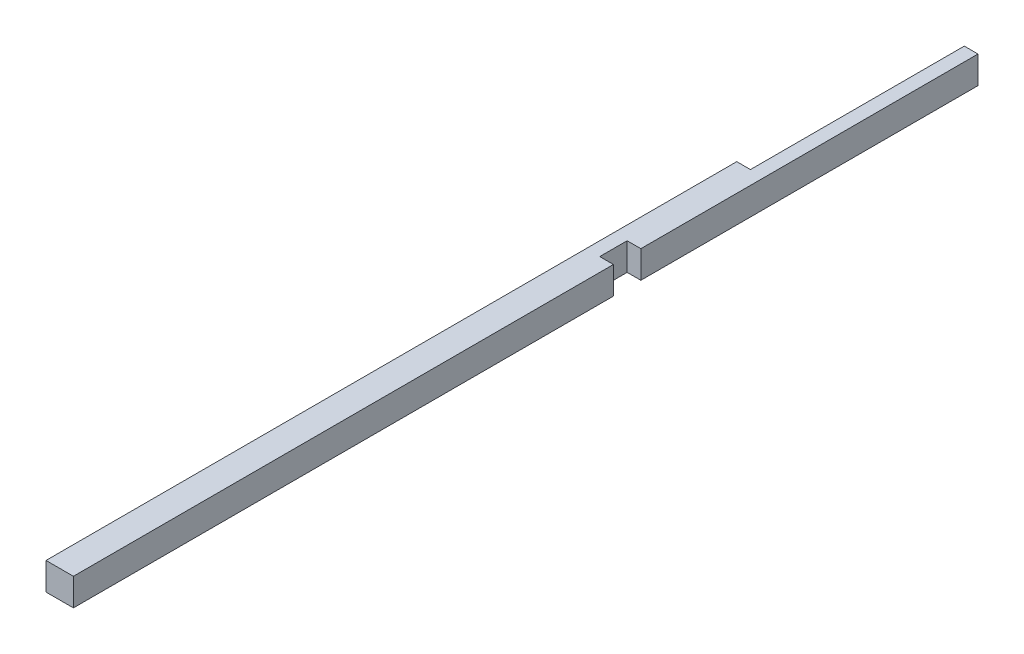
SolidWorks part; units mm, degrees
ref_plane "Plan de face" through (0, 0, 0) normal (0, 0, 1) x (1, 0, 0)
ref_plane "Plan de dessus" through (0, 0, 0) normal (0, 1, 0) x (1, 0, 0)
ref_plane "Plan de droite" through (0, 0, 0) normal (1, 0, 0) x (0, 0, -1)
sketch "Esquisse1" plane through (0, 0, 0) normal (0, 0, 1) x (1, 0, 0)
  line L0 (-5, 5) -> (5, -5) construction
  line L1 (-5, 5) -> (5, 5)
  line L2 (-5, 5) -> (-5, -5)
  line L3 (-5, -5) -> (5, -5)
  line L4 (5, 5) -> (5, -5)
  dimension "D1" = 10
extrude "Boss.-Extru.1" add sketch "Esquisse1" along normal offset from surface (337 mm away) 2 offset beyond the face yes
sketch "Esquisse2" plane through (0, 0, 0) normal (0, 1, 0) x (1, 0, 0)
  line L0 (-5, -85.0125) -> (0, -85.0125)
  line L1 (0, -85.0125) -> (0, -7)
  line L2 (0, -7) -> (5, -7)
  line L3 (5, -7) -> (5, 0)
  line L4 (5, 0) -> (-5, 0)
  line L5 (-5, 0) -> (-5, -85.0125)
  line L6 (5, -337) -> (5, 0) construction
  line L7 (-5, -337) -> (-5, 0) construction
  dimension "D2" = 7
extrude "Enlèv. mat.-Extru.1" cut sketch "Esquisse2" against normal through all and the other way through all
sketch "Esquisse3" plane through (0, -5, 0) normal (0, -1, 0) x (1, 0, 0)
  line L0 (-5, 140) -> (0, 140) construction
  line L1 (0, 130) -> (5, 130)
  line L2 (0, 130) -> (0, 140)
  line L3 (0, 140) -> (5, 140)
  line L4 (5, 130) -> (5, 140)
  line L5 (5, 337) -> (5, 7) construction
extrude "Enlèv. mat.-Extru.2" cut sketch "Esquisse3" against normal through all
